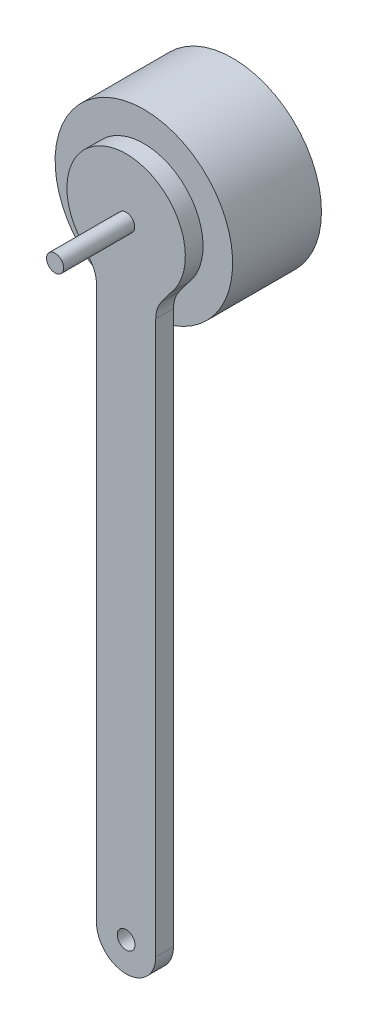
SolidWorks part; units mm, degrees
ref_plane "Front Plane" through (0, 0, 0) normal (0, 0, 1) x (1, 0, 0)
ref_plane "Top Plane" through (0, 0, 0) normal (0, 1, 0) x (1, 0, 0)
ref_plane "Right Plane" through (0, 0, 0) normal (1, 0, 0) x (0, 0, -1)
sketch "Sketch1" plane through (0, 0, 0) normal (0, 0, 1) x (1, 0, 0)
  circle A0 centre (0, 0) radius 15
  dimension "D1" = 30
extrude "Boss-Extrude1" add sketch "Sketch1" along normal blind 15
sketch "Sketch2" plane through (0, 0, 15) normal (0, 0, 1) x (1, 0, 0)
  circle A0 centre (0, 0) radius 1.45
  dimension "D1" = 2.9
extrude "Boss-Extrude2" add sketch "Sketch2" along normal blind 15
sketch "Sketch4" plane through (0, 0, 15) normal (0, 0, 1) x (1, 0, 0)
  line L0 (0, -10) -> (0, -110) construction
  line L1 (5, -10) -> (7.4651, -6.6537)
  line L3 (-5, -10) -> (-5, -110)
  line L4 (-5, -110) -> (5, -110)
  line L5 (5, -10) -> (5, -110)
  line L6 (-5, -10) -> (5, -110) construction
  line L7 (-5, -110) -> (5, -10) construction
  line L8 (-5, -10) -> (-7.4651, -6.6537)
  arc A0 (7.4651, -6.6537) -> (-7.4651, -6.6537) centre (0, 0) ccw
  point P5 (0, -60)
  point P10 (7.4651, -6.6537)
  dimension "D1" = 20
  dimension "D2" = 100
  dimension "D3" = 10
extrude "Boss-Extrude3" add sketch "Sketch4" along normal blind 3
sketch "Sketch5" plane through (0, 0, 18) normal (0, 0, 1) x (1, 0, 0)
  line L0 (0, -110) -> (0, -105) construction
  line L1 (-5, -110) -> (5, -110) construction
  circle A0 centre (0, -105) radius 1.5
  dimension "D2" = 3
  dimension "D1" = 5
extrude "Cut-Extrude1" cut sketch "Sketch5" against normal through all
fillet "Fillet1" radius 5 4 edges at (5, -10, 16.5) (-5, -10, 16.5) (-5, -110, 16.5) (5, -110, 16.5)
